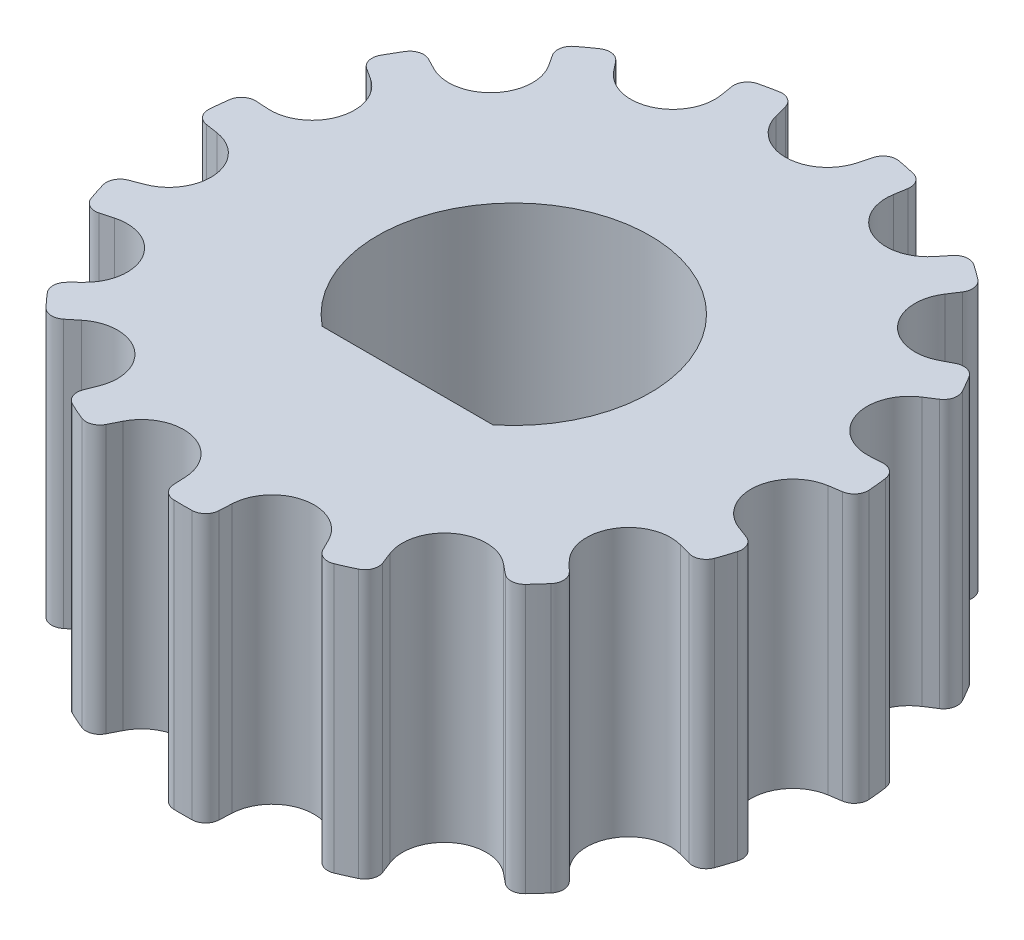
SolidWorks part; units mm, degrees
ref_plane "Front Plane" through (0, 0, 0) normal (0, 0, 1) x (1, 0, 0)
ref_plane "Top Plane" through (0, 0, 0) normal (0, 1, 0) x (1, 0, 0)
ref_plane "Right Plane" through (0, 0, 0) normal (1, 0, 0) x (0, 0, -1)
sketch "Sketch1" plane through (0, 0, 0) normal (0, 1, 0) x (1, 0, 0)
  circle A0 centre (0, 0) radius 7.162
  dimension "D1" = 14.3239
extrude "Boss-Extrude1" add sketch "Sketch1" along normal blind 5.8
sketch "Sketch2" plane through (0, 5.8, 0) normal (0, 1, 0) x (1, 0, 0)
  line L0 (0, 0) -> (0, 7.162) construction
  line L1 (-0.8799, 6.5598) -> (-0.95, 6.8255)
  line L2 (-2.913, 6.5428) -> (-2.913, 7.162)
  line L3 (-2.913, 7.162) -> (2.913, 7.162)
  line L4 (0.8799, 6.5598) -> (0.95, 6.8255)
  line L5 (2.913, 6.5428) -> (2.913, 7.162)
  circle A0 centre (0, 0) radius 7.162 construction
  arc A1 (0.8799, 6.5598) -> (-0.8799, 6.5598) centre (0, 6.792) cw
  arc A2 (-0.95, 6.8255) -> (-1.2943, 7.0441) centre (-1.2401, 6.749) ccw
  arc A4 (0.95, 6.8255) -> (1.2943, 7.0441) centre (1.2401, 6.749) cw
  arc A5 (-1.2943, 7.0441) -> (-2.913, 6.5428) centre (0, 0) ccw
  arc A6 (1.2943, 7.0441) -> (2.913, 6.5428) centre (0, 0) cw
  point P11 (0, 7.162)
  point P19 (0, 5.882)
  dimension "D3" = 0.3
  dimension "D5" = 0.91
  dimension "D2" = 0.95
  dimension "D4" = 1.28
  dimension "D6" = 24
extrude "Cut-Extrude1" cut sketch "Sketch2" against normal through all
pattern_circular "CirPattern1" count 15 over 360 about axis through (0, 5.8, 0) along (0, -1, 0) of "Cut-Extrude1"
sketch "Sketch3" plane through (0, 0, 0) normal (0, -1, 0) x (1, 0, 0)
  line L0 (1.8473, 2.3) -> (-1.8473, 2.3)
  arc A0 (-1.8473, 2.3) -> (1.8473, 2.3) centre (0, 0) ccw
  dimension "D1" = 5.9
  dimension "D2" = 2.3
extrude "Cut-Extrude2" cut sketch "Sketch3" against normal through all
sketch "Sketch5" plane through (0, 0, 0) normal (0, -1, 0) x (1, 0, 0)
  line L60 (5.4179, -3.8244) -> (5.6623, -3.9501)
  line L61 (6.252, -2.9286) -> (6.021, -2.7798)
  line L62 (6.505, -1.2901) -> (6.7794, -1.3055)
  line L63 (6.9027, -0.1325) -> (6.6311, -0.0906)
  line L64 (6.4674, 1.4673) -> (6.7243, 1.5648)
  line L65 (6.3598, 2.6865) -> (6.0946, 2.6144)
  line L66 (5.3115, 3.9709) -> (5.5065, 4.1645)
  line L67 (4.7173, 5.041) -> (4.5044, 4.8673)
  line L68 (3.2371, 5.788) -> (3.3366, 6.0442)
  line L69 (2.2591, 6.5239) -> (2.1352, 6.2786)
  line L70 (0.6031, 6.6042) -> (0.5897, 6.8787)
  line L71 (-0.5897, 6.8787) -> (-0.6031, 6.6042)
  line L72 (-2.1352, 6.2786) -> (-2.2591, 6.5239)
  line L73 (-3.3366, 6.0442) -> (-3.2371, 5.788)
  line L74 (-4.5044, 4.8673) -> (-4.7173, 5.041)
  line L75 (-5.5065, 4.1645) -> (-5.3115, 3.9709)
  line L76 (-6.0946, 2.6144) -> (-6.3598, 2.6865)
  line L77 (-6.7243, 1.5648) -> (-6.4674, 1.4673)
  line L78 (-6.6311, -0.0906) -> (-6.9027, -0.1325)
  line L79 (-6.7794, -1.3055) -> (-6.505, -1.2901)
  line L80 (-6.021, -2.7798) -> (-6.252, -2.9286)
  line L81 (-5.6623, -3.9501) -> (-5.4179, -3.8244)
  line L82 (-4.3698, -4.9885) -> (-4.5203, -5.2184)
  line L83 (-3.5661, -5.9117) -> (-3.394, -5.6974)
  line L84 (-1.963, -6.3345) -> (-2.007, -6.6058)
  line L85 (-0.8533, -6.851) -> (-0.7832, -6.5853)
  line L86 (0.7832, -6.5853) -> (0.8533, -6.851)
  line L87 (2.007, -6.6058) -> (1.963, -6.3345)
  line L88 (3.394, -5.6974) -> (3.5661, -5.9117)
  line L89 (4.5203, -5.2184) -> (4.3698, -4.9885)
  line L90 (5.4179, -3.8244) -> (5.6623, -3.9501)
  line L91 (6.252, -2.9286) -> (6.021, -2.7798)
  line L92 (6.505, -1.2901) -> (6.7794, -1.3055)
  line L93 (6.9027, -0.1325) -> (6.6311, -0.0906)
  line L94 (6.4674, 1.4673) -> (6.7243, 1.5648)
  line L95 (6.3598, 2.6865) -> (6.0946, 2.6144)
  line L96 (5.3115, 3.9709) -> (5.5065, 4.1645)
  line L97 (4.7173, 5.041) -> (4.5044, 4.8673)
  line L98 (3.2371, 5.788) -> (3.3366, 6.0442)
  line L99 (2.2591, 6.5239) -> (2.1352, 6.2786)
  line L100 (0.6031, 6.6042) -> (0.5897, 6.8787)
  line L101 (-0.5897, 6.8787) -> (-0.6031, 6.6042)
  line L102 (-2.1352, 6.2786) -> (-2.2591, 6.5239)
  line L103 (-3.3366, 6.0442) -> (-3.2371, 5.788)
  line L104 (-4.5044, 4.8673) -> (-4.7173, 5.041)
  line L105 (-5.5065, 4.1645) -> (-5.3115, 3.9709)
  line L106 (-6.0946, 2.6144) -> (-6.3598, 2.6865)
  line L107 (-6.7243, 1.5648) -> (-6.4674, 1.4673)
  line L108 (-6.6311, -0.0906) -> (-6.9027, -0.1325)
  line L109 (-6.7794, -1.3055) -> (-6.505, -1.2901)
  line L110 (-6.021, -2.7798) -> (-6.252, -2.9286)
  line L111 (-5.6623, -3.9501) -> (-5.4179, -3.8244)
  line L112 (-4.3698, -4.9885) -> (-4.5203, -5.2184)
  line L113 (-3.5661, -5.9117) -> (-3.394, -5.6974)
  line L114 (-1.963, -6.3345) -> (-2.007, -6.6058)
  line L115 (-0.8533, -6.851) -> (-0.7832, -6.5853)
  line L116 (0.7832, -6.5853) -> (0.8533, -6.851)
  line L117 (2.007, -6.6058) -> (1.963, -6.3345)
  line L118 (3.394, -5.6974) -> (3.5661, -5.9117)
  line L119 (4.5203, -5.2184) -> (4.3698, -4.9885)
  circle A60 centre (0, 0) radius 3.9038
  arc A120 (5.6623, -3.9501) -> (6.186, -3.8039) centre (5.8452, -3.5944) ccw
  arc A121 (6.186, -3.8039) -> (6.3873, -3.4553) centre (0, 0) ccw
  arc A122 (6.3873, -3.4553) -> (6.252, -2.9286) centre (6.0355, -3.2649) ccw
  arc A123 (6.505, -1.2901) -> (6.021, -2.7798) centre (6.4595, -2.0988) ccw
  arc A124 (6.7794, -1.3055) -> (7.1984, -0.959) centre (6.8019, -0.9062) ccw
  arc A125 (7.1984, -0.959) -> (7.2405, -0.5586) centre (0, 0) ccw
  arc A126 (7.2405, -0.5586) -> (6.9027, -0.1325) centre (6.8416, -0.5278) ccw
  arc A127 (6.4674, 1.4673) -> (6.6311, -0.0906) centre (6.7548, 0.71) ccw
  arc A128 (6.7243, 1.5648) -> (6.9661, 2.0518) centre (6.5824, 1.9387) ccw
  arc A129 (6.9661, 2.0518) -> (6.8417, 2.4347) centre (0, 0) ccw
  arc A130 (6.8417, 2.4347) -> (6.3598, 2.6865) centre (6.4648, 2.3006) ccw
  arc A131 (5.3115, 3.9709) -> (6.0946, 2.6144) centre (5.882, 3.396) ccw
  arc A132 (5.5065, 4.1645) -> (5.5293, 4.7077) centre (5.2248, 4.4484) ccw
  arc A133 (5.5293, 4.7077) -> (5.2599, 5.0069) centre (0, 0) ccw
  arc A134 (5.2599, 5.0069) -> (4.7173, 5.041) centre (4.9702, 4.7312) ccw
  arc A135 (3.2371, 5.788) -> (4.5044, 4.8673) centre (3.9922, 5.4948) ccw
  arc A136 (3.3366, 6.0442) -> (3.1365, 6.5497) centre (2.9637, 6.1889) ccw
  arc A137 (3.1365, 6.5497) -> (2.7687, 6.7135) centre (0, 0) ccw
  arc A138 (2.7687, 6.7135) -> (2.2591, 6.5239) centre (2.6162, 6.3437) ccw
  arc A139 (0.6031, 6.6042) -> (2.1352, 6.2786) centre (1.4121, 6.6436) ccw
  arc A140 (0.5897, 6.8787) -> (0.2013, 7.2592) centre (0.1902, 6.8593) ccw
  arc A141 (0.2013, 7.2592) -> (-0.2013, 7.2592) centre (0, 0) ccw
  arc A142 (-0.2013, 7.2592) -> (-0.5897, 6.8787) centre (-0.1902, 6.8593) ccw
  arc A143 (-2.1352, 6.2786) -> (-0.6031, 6.6042) centre (-1.4121, 6.6436) ccw
  arc A144 (-2.2591, 6.5239) -> (-2.7687, 6.7135) centre (-2.6162, 6.3437) ccw
  arc A145 (-2.7687, 6.7135) -> (-3.1365, 6.5497) centre (0, 0) ccw
  arc A146 (-3.1365, 6.5497) -> (-3.3366, 6.0442) centre (-2.9637, 6.1889) ccw
  arc A147 (-4.5044, 4.8673) -> (-3.2371, 5.788) centre (-3.9922, 5.4948) ccw
  arc A148 (-4.7173, 5.041) -> (-5.2599, 5.0069) centre (-4.9702, 4.7312) ccw
  arc A149 (-5.2599, 5.0069) -> (-5.5293, 4.7077) centre (0, 0) ccw
  arc A150 (-5.5293, 4.7077) -> (-5.5065, 4.1645) centre (-5.2248, 4.4484) ccw
  arc A151 (-6.0946, 2.6144) -> (-5.3115, 3.9709) centre (-5.882, 3.396) ccw
  arc A152 (-6.3598, 2.6865) -> (-6.8417, 2.4347) centre (-6.4648, 2.3006) ccw
  arc A153 (-6.8417, 2.4347) -> (-6.9661, 2.0518) centre (0, 0) ccw
  arc A154 (-6.9661, 2.0518) -> (-6.7243, 1.5648) centre (-6.5824, 1.9387) ccw
  arc A155 (-6.6311, -0.0906) -> (-6.4674, 1.4673) centre (-6.7548, 0.71) ccw
  arc A156 (-6.9027, -0.1325) -> (-7.2405, -0.5586) centre (-6.8416, -0.5278) ccw
  arc A157 (-7.2405, -0.5586) -> (-7.1984, -0.959) centre (0, 0) ccw
  arc A158 (-7.1984, -0.959) -> (-6.7794, -1.3055) centre (-6.8019, -0.9062) ccw
  arc A159 (-6.021, -2.7798) -> (-6.505, -1.2901) centre (-6.4595, -2.0988) ccw
  arc A160 (-6.252, -2.9286) -> (-6.3873, -3.4553) centre (-6.0355, -3.2649) ccw
  arc A161 (-6.3873, -3.4553) -> (-6.186, -3.8039) centre (0, 0) ccw
  arc A162 (-6.186, -3.8039) -> (-5.6623, -3.9501) centre (-5.8452, -3.5944) ccw
  arc A163 (-4.3698, -4.9885) -> (-5.4179, -3.8244) centre (-5.0474, -4.5447) ccw
  arc A164 (-4.5203, -5.2184) -> (-4.4297, -5.7545) centre (-4.1857, -5.4375) ccw
  arc A165 (-4.4297, -5.7545) -> (-4.104, -5.9911) centre (0, 0) ccw
  arc A166 (-4.104, -5.9911) -> (-3.5661, -5.9117) centre (-3.8779, -5.6611) ccw
  arc A167 (-1.963, -6.3345) -> (-3.394, -5.6974) centre (-2.7625, -6.2048) ccw
  arc A168 (-2.007, -6.6058) -> (-1.7062, -7.0587) centre (-1.6122, -6.6699) ccw
  arc A169 (-1.7062, -7.0587) -> (-1.3124, -7.1424) centre (0, 0) ccw
  arc A170 (-1.3124, -7.1424) -> (-0.8533, -6.851) centre (-1.2401, -6.749) ccw
  arc A171 (0.7832, -6.5853) -> (-0.7832, -6.5853) centre (0, -6.792) ccw
  arc A172 (0.8533, -6.851) -> (1.3124, -7.1424) centre (1.2401, -6.749) ccw
  arc A173 (1.3124, -7.1424) -> (1.7062, -7.0587) centre (0, 0) ccw
  arc A174 (1.7062, -7.0587) -> (2.007, -6.6058) centre (1.6122, -6.6699) ccw
  arc A175 (3.394, -5.6974) -> (1.963, -6.3345) centre (2.7625, -6.2048) ccw
  arc A176 (3.5661, -5.9117) -> (4.104, -5.9911) centre (3.8779, -5.6611) ccw
  arc A177 (4.104, -5.9911) -> (4.4297, -5.7545) centre (0, 0) ccw
  arc A178 (4.4297, -5.7545) -> (4.5203, -5.2184) centre (4.1857, -5.4375) ccw
  arc A179 (5.4179, -3.8244) -> (4.3698, -4.9885) centre (5.0474, -4.5447) ccw
  arc A180 (5.6623, -3.9501) -> (6.186, -3.8039) centre (5.8452, -3.5944) ccw
  arc A181 (6.186, -3.8039) -> (6.3873, -3.4553) centre (0, 0) ccw
  arc A182 (6.3873, -3.4553) -> (6.252, -2.9286) centre (6.0355, -3.2649) ccw
  arc A183 (6.505, -1.2901) -> (6.021, -2.7798) centre (6.4595, -2.0988) ccw
  arc A184 (6.7794, -1.3055) -> (7.1984, -0.959) centre (6.8019, -0.9062) ccw
  arc A185 (7.1984, -0.959) -> (7.2405, -0.5586) centre (0, 0) ccw
  arc A186 (7.2405, -0.5586) -> (6.9027, -0.1325) centre (6.8416, -0.5278) ccw
  arc A187 (6.4674, 1.4673) -> (6.6311, -0.0906) centre (6.7548, 0.71) ccw
  arc A188 (6.7243, 1.5648) -> (6.9661, 2.0518) centre (6.5824, 1.9387) ccw
  arc A189 (6.9661, 2.0518) -> (6.8417, 2.4347) centre (0, 0) ccw
  arc A190 (6.8417, 2.4347) -> (6.3598, 2.6865) centre (6.4648, 2.3006) ccw
  arc A191 (5.3115, 3.9709) -> (6.0946, 2.6144) centre (5.882, 3.396) ccw
  arc A192 (5.5065, 4.1645) -> (5.5293, 4.7077) centre (5.2248, 4.4484) ccw
  arc A193 (5.5293, 4.7077) -> (5.2599, 5.0069) centre (0, 0) ccw
  arc A194 (5.2599, 5.0069) -> (4.7173, 5.041) centre (4.9702, 4.7312) ccw
  arc A195 (3.2371, 5.788) -> (4.5044, 4.8673) centre (3.9922, 5.4948) ccw
  arc A196 (3.3366, 6.0442) -> (3.1365, 6.5497) centre (2.9637, 6.1889) ccw
  arc A197 (3.1365, 6.5497) -> (2.7687, 6.7135) centre (0, 0) ccw
  arc A198 (2.7687, 6.7135) -> (2.2591, 6.5239) centre (2.6162, 6.3437) ccw
  arc A199 (0.6031, 6.6042) -> (2.1352, 6.2786) centre (1.4121, 6.6436) ccw
  arc A200 (0.5897, 6.8787) -> (0.2013, 7.2592) centre (0.1902, 6.8593) ccw
  arc A201 (0.2013, 7.2592) -> (-0.2013, 7.2592) centre (0, 0) ccw
  arc A202 (-0.2013, 7.2592) -> (-0.5897, 6.8787) centre (-0.1902, 6.8593) ccw
  arc A203 (-2.1352, 6.2786) -> (-0.6031, 6.6042) centre (-1.4121, 6.6436) ccw
  arc A204 (-2.2591, 6.5239) -> (-2.7687, 6.7135) centre (-2.6162, 6.3437) ccw
  arc A205 (-2.7687, 6.7135) -> (-3.1365, 6.5497) centre (0, 0) ccw
  arc A206 (-3.1365, 6.5497) -> (-3.3366, 6.0442) centre (-2.9637, 6.1889) ccw
  arc A207 (-4.5044, 4.8673) -> (-3.2371, 5.788) centre (-3.9922, 5.4948) ccw
  arc A208 (-4.7173, 5.041) -> (-5.2599, 5.0069) centre (-4.9702, 4.7312) ccw
  arc A209 (-5.2599, 5.0069) -> (-5.5293, 4.7077) centre (0, 0) ccw
  arc A210 (-5.5293, 4.7077) -> (-5.5065, 4.1645) centre (-5.2248, 4.4484) ccw
  arc A211 (-6.0946, 2.6144) -> (-5.3115, 3.9709) centre (-5.882, 3.396) ccw
  arc A212 (-6.3598, 2.6865) -> (-6.8417, 2.4347) centre (-6.4648, 2.3006) ccw
  arc A213 (-6.8417, 2.4347) -> (-6.9661, 2.0518) centre (0, 0) ccw
  arc A214 (-6.9661, 2.0518) -> (-6.7243, 1.5648) centre (-6.5824, 1.9387) ccw
  arc A215 (-6.6311, -0.0906) -> (-6.4674, 1.4673) centre (-6.7548, 0.71) ccw
  arc A216 (-6.9027, -0.1325) -> (-7.2405, -0.5586) centre (-6.8416, -0.5278) ccw
  arc A217 (-7.2405, -0.5586) -> (-7.1984, -0.959) centre (0, 0) ccw
  arc A218 (-7.1984, -0.959) -> (-6.7794, -1.3055) centre (-6.8019, -0.9062) ccw
  arc A219 (-6.021, -2.7798) -> (-6.505, -1.2901) centre (-6.4595, -2.0988) ccw
  arc A220 (-6.252, -2.9286) -> (-6.3873, -3.4553) centre (-6.0355, -3.2649) ccw
  arc A221 (-6.3873, -3.4553) -> (-6.186, -3.8039) centre (0, 0) ccw
  arc A222 (-6.186, -3.8039) -> (-5.6623, -3.9501) centre (-5.8452, -3.5944) ccw
  arc A223 (-4.3698, -4.9885) -> (-5.4179, -3.8244) centre (-5.0474, -4.5447) ccw
  arc A224 (-4.5203, -5.2184) -> (-4.4297, -5.7545) centre (-4.1857, -5.4375) ccw
  arc A225 (-4.4297, -5.7545) -> (-4.104, -5.9911) centre (0, 0) ccw
  arc A226 (-4.104, -5.9911) -> (-3.5661, -5.9117) centre (-3.8779, -5.6611) ccw
  arc A227 (-1.963, -6.3345) -> (-3.394, -5.6974) centre (-2.7625, -6.2048) ccw
  arc A228 (-2.007, -6.6058) -> (-1.7062, -7.0587) centre (-1.6122, -6.6699) ccw
  arc A229 (-1.7062, -7.0587) -> (-1.3124, -7.1424) centre (0, 0) ccw
  arc A230 (-1.3124, -7.1424) -> (-0.8533, -6.851) centre (-1.2401, -6.749) ccw
  arc A231 (0.7832, -6.5853) -> (-0.7832, -6.5853) centre (0, -6.792) ccw
  arc A232 (0.8533, -6.851) -> (1.3124, -7.1424) centre (1.2401, -6.749) ccw
  arc A233 (1.3124, -7.1424) -> (1.7062, -7.0587) centre (0, 0) ccw
  arc A234 (1.7062, -7.0587) -> (2.007, -6.6058) centre (1.6122, -6.6699) ccw
  arc A235 (3.394, -5.6974) -> (1.963, -6.3345) centre (2.7625, -6.2048) ccw
  arc A236 (3.5661, -5.9117) -> (4.104, -5.9911) centre (3.8779, -5.6611) ccw
  arc A237 (4.104, -5.9911) -> (4.4297, -5.7545) centre (0, 0) ccw
  arc A238 (4.4297, -5.7545) -> (4.5203, -5.2184) centre (4.1857, -5.4375) ccw
  arc A239 (5.4179, -3.8244) -> (4.3698, -4.9885) centre (5.0474, -4.5447) ccw
  dimension "D1" = 0.1
extrude "Boss-Extrude2" [suppressed] add sketch "Sketch5" against normal up to surface (5.8 mm away) up to face at (0, 5.8, -0.325)
equation "\"smallPulleyTeeth\"= 15"
equation "\"largePulleyTeeth\"= 30"
equation "\"eighthThick\"= 2.9mm"
equation "\"D1@Sketch1\"=3*\"smallPulleyTeeth\"/pi"
equation "\"D1@Boss-Extrude1\" = \"eighthThick\" * 2"
equation "\"D6@Sketch2\"=360/\"smallPulleyTeeth\""
equation "\"quarterThick\"=5.9mm"
equation "\"D1@CirPattern1\"=\"smallPulleyTeeth\""
equation "\"sixteenthThick\" = 1.7mm"
equation "\"OD\" = 145mm"
equation "\"puckAngle\" = 60.5deg"
equation "\"puckDiam\" = 76.5mm"
equation "\"axlePress\" = 5.9mm"
equation "\"press\" = 0.2mm"
equation "\"wheelClear\" = 0.3mm"
equation "\"10-32clear\" = 4.5mm"
equation "\"6-32clear\" = 3.3mm"
equation "\"8-32clear\" = 4.0mm"
equation "\"wheelHeight\" = 24mm"
equation "\"D1@Sketch3\"=\"axlePress\""
